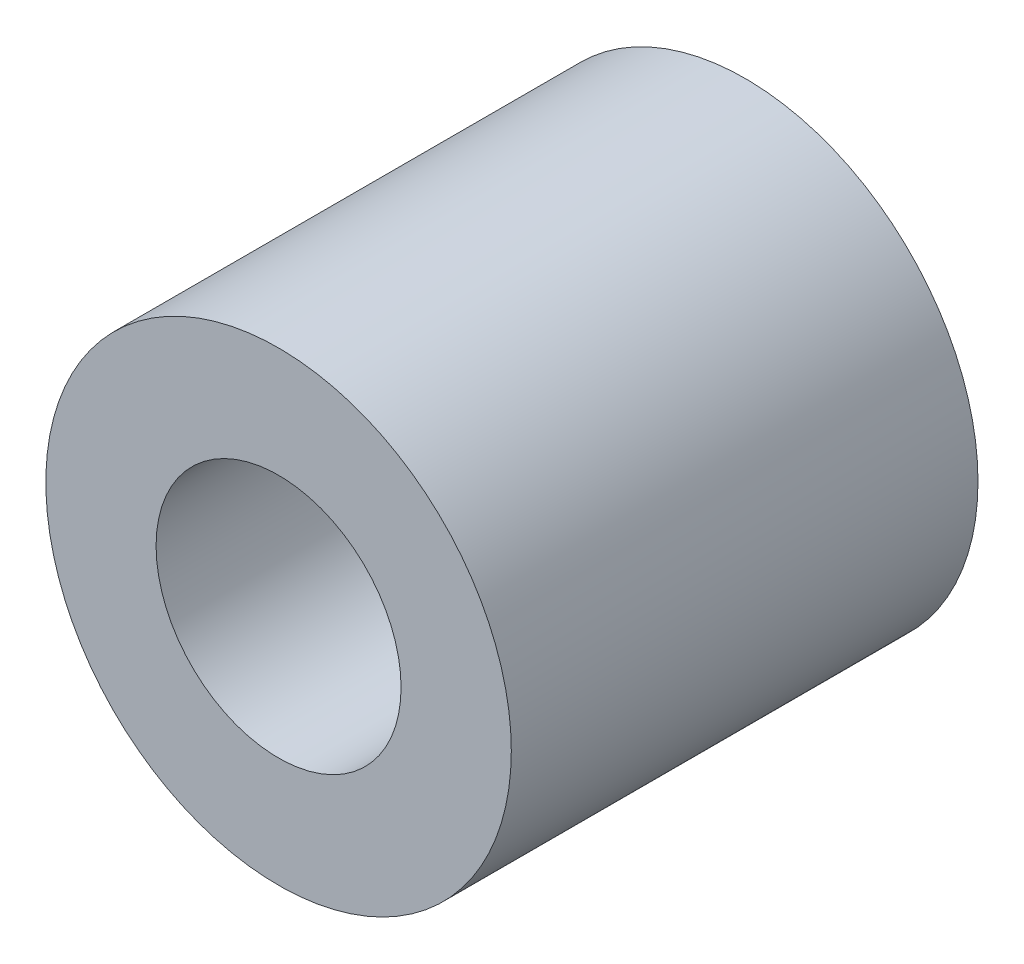
SolidWorks part; units mm, degrees
material "Nylon 6/10"
ref_plane "Front Plane" through (0, 0, 0) normal (0, 0, 1) x (1, 0, 0)
ref_plane "Top Plane" through (0, 0, 0) normal (0, 1, 0) x (1, 0, 0)
ref_plane "Right Plane" through (0, 0, 0) normal (1, 0, 0) x (0, 0, -1)
sketch "Sketch1" plane through (0, 0, 0) normal (0, 1, 0) x (1, 0, 0)
  line L0 (4.75, 4.7625) -> (2.5, 4.7625)
  line L1 (2.5, 4.7625) -> (2.5, -4.7625)
  line L2 (2.5, -4.7625) -> (4.75, -4.7625)
  line L3 (4.75, -4.7625) -> (4.75, 4.7625)
  line L4 (0, 4.7625) -> (0, -4.7625) construction
revolve "Revolve1" add sketch "Sketch1" angle 360 about L4 reverse direction yes
